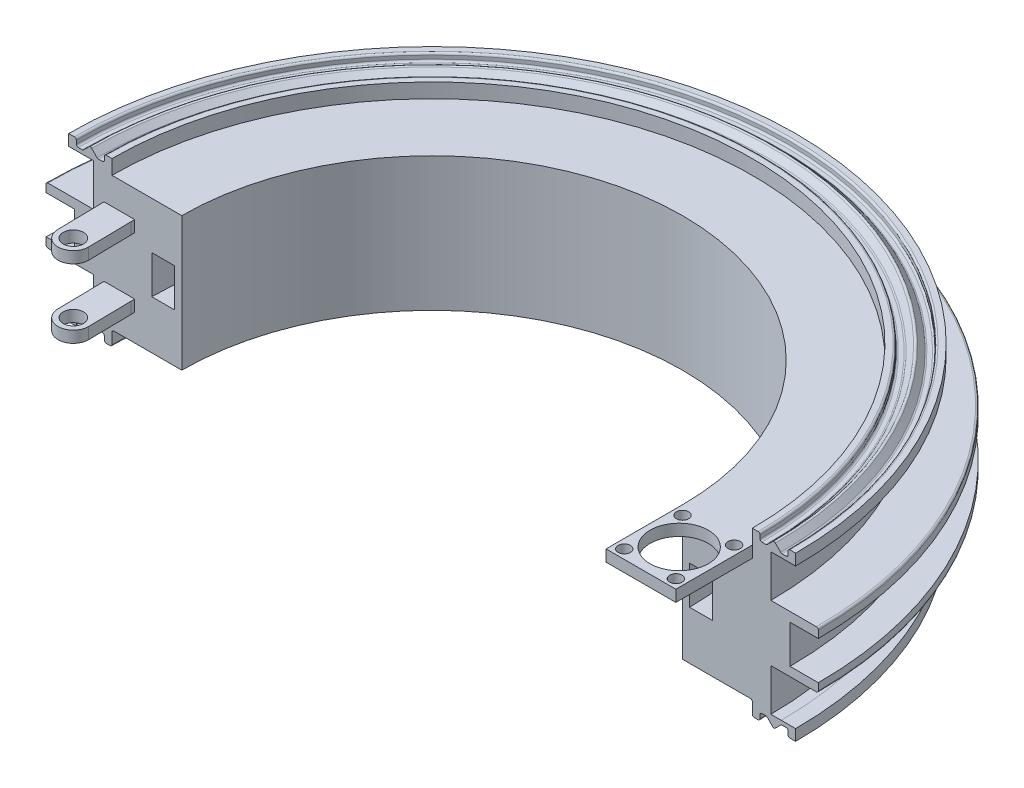
SolidWorks part; units mm, degrees
ref_plane "Front Plane" through (0, 0, 0) normal (0, 0, 1) x (1, 0, 0)
ref_plane "Top Plane" through (0, 0, 0) normal (0, 1, 0) x (1, 0, 0)
ref_plane "Right Plane" through (0, 0, 0) normal (1, 0, 0) x (0, 0, -1)
sketch "Sketch1" plane through (0, 0, 0) normal (0, 0, 1) x (1, 0, 0)
  line L0 (0, 21.2431) -> (0, -20.7935) construction
  line L1 (0, 21.2431) -> (0, -13.7569)
  line L12 (-28.1024, -1.3005) -> (-28.1024, 8.6995)
  line L14 (-35.4985, 8.6995) -> (-35.4985, 11.1239)
  line L23 (0, 3.7431) -> (-36.1577, 3.7431) construction
  line L25 (-7.8424, 8.9508) -> (-1.8424, 8.9508)
  line L26 (-7.8424, 8.9508) -> (-7.8424, -1.0492)
  line L27 (-7.8424, -1.0492) -> (-1.8424, -1.0492)
  line L28 (-1.8424, 8.9508) -> (-1.8424, -1.0492)
  line L29 (-22, 23.1426) -> (-23.9092, 25.0518)
  line L30 (-23.9092, 25.0518) -> (-25.8184, 23.1426)
  line L32 (-25.8184, 22.1426) -> (-23.0909, 22.1426)
  line L33 (-23.0909, 22.1426) -> (-23.0909, 11.1239)
  line L34 (-23.0909, 11.1239) -> (-35.4985, 11.1239)
  line L35 (-35.4985, -3.6377) -> (-23.0909, -3.6377)
  line L42 (-35.4985, -3.6377) -> (-35.4985, -1.3005)
  line L43 (-35.4985, -1.3005) -> (-28.1024, -1.3005)
  line L44 (-35.4985, 8.6995) -> (-28.1024, 8.6995)
  line L45 (-22, 23.1426) -> (-20.25, 23.1426)
  line L46 (-20.25, 23.1426) -> (-20.25, 25.0518)
  line L47 (-18.25, 25.0518) -> (-18.25, 21.2431)
  line L48 (-18.25, 21.2431) -> (0, 21.2431)
  line L49 (-20.25, 25.0518) -> (-18.25, 25.0518)
  line L50 (-25.8184, 23.1426) -> (-27.5684, 23.1426)
  line L51 (-27.5684, 23.1426) -> (-27.5684, 25.0518)
  line L52 (-27.5684, 25.0518) -> (-29.5684, 25.0518)
  line L53 (-29.5684, 25.0518) -> (-29.5684, 22.1426)
  line L54 (-29.5684, 22.1426) -> (-25.8184, 22.1426)
  line L65 (-29.5684, -14.6564) -> (-25.8184, -14.6564)
  line L66 (-29.5684, -17.5655) -> (-29.5684, -14.6564)
  line L67 (-27.5684, -17.5655) -> (-29.5684, -17.5655)
  line L68 (-27.5684, -15.6564) -> (-27.5684, -17.5655)
  line L69 (-25.8184, -15.6564) -> (-27.5684, -15.6564)
  line L70 (-20.25, -17.5655) -> (-18.25, -17.5655)
  line L71 (-18.25, -13.7569) -> (0, -13.7569)
  line L72 (-18.25, -17.5655) -> (-18.25, -13.7569)
  line L73 (-20.25, -15.6564) -> (-20.25, -17.5655)
  line L74 (-22, -15.6564) -> (-20.25, -15.6564)
  line L75 (-23.0909, -14.6564) -> (-23.0909, -3.6377)
  line L76 (-25.8184, -14.6564) -> (-23.0909, -14.6564)
  line L77 (-23.9092, -17.5655) -> (-25.8184, -15.6564)
  line L78 (-22, -15.6564) -> (-23.9092, -17.5655)
  line L79 (-35.4985, 8.6995) -> (-35.4985, -5.9646) construction
  dimension "D1" = 35
  dimension "D2" = 1.75
  dimension "D3" = 1
  dimension "D4" = 2.7
  dimension "D5" = 2.7
  dimension "D6" = 2
  dimension "D7" = 2
  dimension "D8" = 10
  dimension "D10" = 10
  dimension "D11" = 6
sketch "Sketch3" plane through (0, 0, 0) normal (0, 1, 0) x (1, 0, 0)
  arc A0 (0, 0) -> (130.92, 0) centre (65.46, 0) cw
sweep "Sweep3" add profiles "Sketch1" path "Sketch3"
sketch "Sketch13" plane through (0, 0, 0) normal (0, 0, 1) x (1, 0, 0)
  line L4 (-7.8424, 3.9508) -> (-7.8424, 18.9333) construction
  line L5 (-7.8424, -1.0492) -> (-7.8424, 8.9508) construction
  line L6 (-7.8424, 18.9333) -> (-7.8424, -5.0069) construction
  line L7 (-28.1024, 3.6995) -> (-1.1121, 3.6995) construction
  line L8 (-28.1024, 8.6995) -> (-28.1024, -1.3005) construction
  line L9 (-16.2449, 7.1426) -> (-16.2449, 2.1426) construction
  line L15 (-20.3051, -3.8005) -> (-12.3051, -3.8005)
  line L16 (-12.3051, -3.8005) -> (-12.3051, -6.8005)
  line L22 (-12.3051, -6.8005) -> (-20.3051, -6.8005)
  line L23 (-20.3051, -6.8005) -> (-20.3051, -3.8005)
  line L24 (-20.3051, 11.1995) -> (-12.3051, 11.1995)
  line L25 (-20.3051, 14.1995) -> (-20.3051, 11.1995)
  line L26 (-12.3051, 14.1995) -> (-20.3051, 14.1995)
  line L27 (-12.3051, 11.1995) -> (-12.3051, 14.1995)
  dimension "D1" = 3
  dimension "D2" = 8
  dimension "D3" = 7.5
ref_plane "Plane3" through (0, 3.6995, 0) normal (0, 1, 0) x (1, 0, 0)
sketch "Sketch17" plane through (0, 0, 0) normal (0, 0, 1) x (1, 0, 0)
  line L3 (130.92, 21.2431) -> (149.17, 21.2431)
  line L11 (149.17, 21.2431) -> (149.17, 18.2431)
  line L12 (149.17, 18.2431) -> (130.92, 18.2431)
  line L13 (130.92, -13.7569) -> (130.92, 21.2431) construction
  line L14 (130.92, 18.2431) -> (130.92, 21.2431)
  dimension "D1" = 3
extrude "Boss-Extrude5" add sketch "Sketch17" along normal blind 20
fillet "Fillet1" radius 0.5 1 edges at (65.46, 25.0518, -89.3692)
fillet "Fillet2" radius 0.5 1 edges at (65.46, 23.1426, -91.2784)
fillet "Fillet3" radius 0.5 1 edges at (65.46, 23.1426, -93.0284)
fillet "Fillet4" radius 0.5 2 edges at (65.46, 23.1426, -85.71) (65.46, 23.1426, -87.46)
fillet "Fillet5" radius 0.5 3 edges at (65.46, -17.5655, -85.71) (65.46, -15.6564, -87.46) (65.46, -17.5655, -89.3692)
fillet "Fillet6" radius 0.5 3 edges at (65.46, -13.7569, -83.71) (65.46, -17.5655, -83.71) (65.46, -15.6564, -85.71)
fillet "Fillet7" radius 0.5 3 edges at (65.46, -15.6564, -91.2784) (65.46, -17.5655, -93.0284) (65.46, -15.6564, -93.0284)
fillet "Fillet9" radius 0.5 2 edges at (65.46, -3.6377, -100.9585) (65.46, 11.1239, -100.9585)
fillet "Fillet10" radius 0.5 2 edges at (65.46, 25.0518, -93.0284) (65.46, 25.0518, -85.71)
extrude "Boss-Extrude6" add sketch "Sketch13" along normal blind 1
sketch "Sketch19" plane through (0, 14.1995, 0) normal (0, 1, 0) x (1, 0, 0)
  line L0 (-20.3051, -1) -> (-20.1153, -12.2376)
  line L1 (-12.3051, -1) -> (-12.1153, -12.2376)
  circle A0 centre (-16.1153, -12.2376) radius 2.65
  circle A1 centre (-16.1153, -12.2376) radius 4
  line M5 (-20.3051, -1) -> (-12.3051, -1)
  dimension "D1" = 5.3
extrude "Boss-Extrude7" add sketch "Sketch19" against normal blind 3 contours A1 L1 L0 M5 | L1 A1 A0 region at (-16.2471, 14.1995, 5.0972) region at (-16.181, 14.1995, 8.3513)
mirror "Mirror1" about plane through (0, 3.6995, 0) normal (0, 1, 0) of "Boss-Extrude6", "Boss-Extrude7"
sketch "Sketch20" plane through (0, 18.2431, 0) normal (0, -1, 0) x (1, 0, 0)
  line L0 (140.045, 20) -> (140.045, 0) construction
  line L1 (130.92, 20) -> (149.17, 20) construction
  line L2 (130.92, 0) -> (149.17, 0) construction
  line L3 (130.92, 10) -> (149.17, 10) construction
  line L4 (130.92, 20) -> (130.92, 0) construction
  line L5 (149.17, 20) -> (149.17, 0) construction
  circle A0 centre (140.045, 10) radius 7.6127
  circle A1 centre (133.3021, 2.3873) radius 1.6052
  circle A2 centre (133.3021, 17.6127) radius 1.6052
  circle A3 centre (146.7878, 17.6127) radius 1.6052
  circle A4 centre (146.7878, 2.3873) radius 1.6052
extrude "Cut-Extrude2" cut sketch "Sketch20" against normal blind 13
